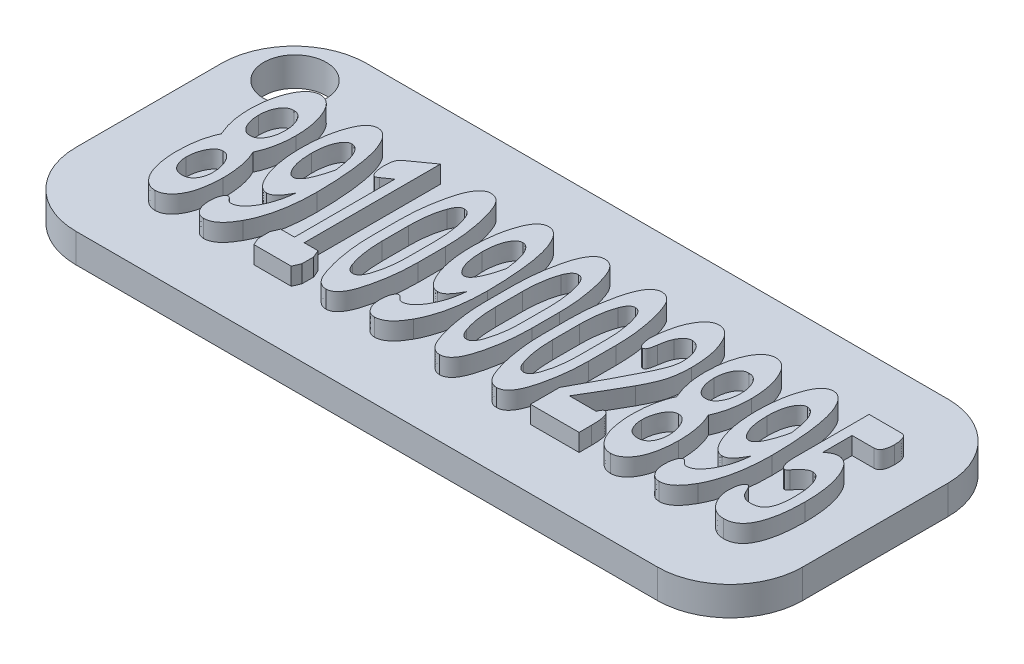
SolidWorks part; units mm, degrees
ref_plane "Спереди" through (0, 0, 0) normal (0, 0, 1) x (1, 0, 0)
ref_plane "Сверху" through (0, 0, 0) normal (0, 1, 0) x (1, 0, 0)
ref_plane "Справа" through (0, 0, 0) normal (1, 0, 0) x (0, 0, -1)
other "Configuration Table"
sketch "Эскиз1" plane through (0, 0, 0) normal (0, 1, 0) x (1, 0, 0)
  line L1 (0, 0) -> (50, 0)
  line L2 (0, 0) -> (0, 20)
  line L3 (0, 20) -> (50, 20)
  line L4 (50, 0) -> (50, 20)
  dimension "D1" = 20
  dimension "D2" = 50
extrude "Бобышка-Вытянуть1" add sketch "Эскиз1" along normal blind 2 contours L2 L3 L4 L1
sketch "Эскиз2" plane through (0, 2, 0) normal (0, 1, 0) x (1, 0, 0)
  line L0 (-2.8341, 4.1295) -> (51.2146, 4.1295) construction
  text T0 "<b> 89109002895</b>" font "Courier New" height in points 48
extrude "номер" add sketch "Эскиз2" along normal blind 1.2
fillet "Скругление1" radius 5 1 edges at (0, 1, -20)
fillet "Скругление2" radius 5 1 edges at (0, 1, 0)
fillet "Скругление3" radius 5 1 edges at (50, 1, -20)
fillet "Скругление4" radius 5 1 edges at (50, 1, 0)
sketch "Эскиз4" plane through (0, 2, 0) normal (0, 1, 0) x (1, 0, 0)
  circle A0 centre (3.5425, 16.5284) radius 2.1519
extrude "Вырез-Вытянуть1" cut sketch "Эскиз4" against normal blind 3
